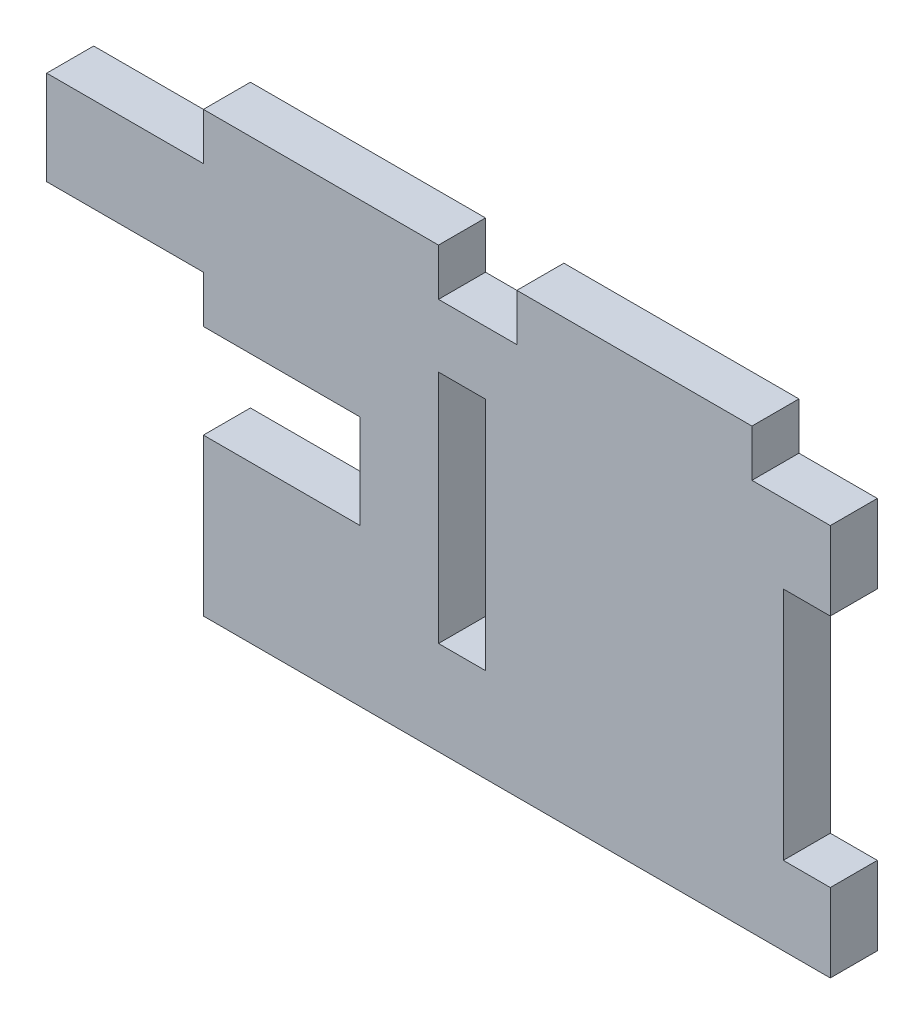
SolidWorks part; units mm, degrees
ref_plane "Front Plane" through (0, 0, 0) normal (0, 0, 1) x (1, 0, 0)
ref_plane "Top Plane" through (0, 0, 0) normal (0, 1, 0) x (1, 0, 0)
ref_plane "Right Plane" through (0, 0, 0) normal (1, 0, 0) x (0, 0, -1)
sketch "Sketch2" plane through (0, 0, 0) normal (0, 0, 1) x (1, 0, 0)
  line L0 (-22.0738, 7.8629) -> (-22.0738, 10.8629)
  line L1 (17.9262, 7.8629) -> (12.9262, 7.8629)
  line L2 (17.9262, 7.8629) -> (17.9262, -17.1371)
  line L3 (17.9262, -17.1371) -> (-32.0738, -17.1371)
  line L4 (-32.0738, 7.8629) -> (-32.0738, -17.1371)
  line L5 (17.9262, 2.8629) -> (14.9262, 2.8629)
  line L6 (-22.0738, 10.8629) -> (-7.0738, 10.8629)
  line L7 (17.9262, -12.1371) -> (14.9262, -12.1371)
  line L8 (14.9262, 2.8629) -> (14.9262, -12.1371)
  line L9 (-4.0738, -11.1532) -> (-7.0738, -11.1532)
  line L10 (-4.0738, -11.1532) -> (-4.0738, 3.8468)
  line L11 (-4.0738, 3.8468) -> (-7.0738, 3.8468)
  line L12 (-7.0738, -11.1532) -> (-7.0738, 3.8468)
  line L13 (-27.0738, -1.1371) -> (-12.0738, -1.1371)
  line L14 (-27.0738, -1.1371) -> (-27.0738, -7.1371)
  line L15 (-27.0738, -7.1371) -> (-12.0738, -7.1371)
  line L16 (-12.0738, -1.1371) -> (-12.0738, -7.1371)
  line L17 (-7.0738, 10.8629) -> (-7.0738, 7.8629)
  line L18 (-2.0738, 7.8629) -> (-2.0738, 10.8629)
  line L19 (-2.0738, 10.8629) -> (12.9262, 10.8629)
  line L20 (12.9262, 10.8629) -> (12.9262, 7.8629)
  line L21 (-22.0738, 7.8629) -> (-32.0738, 7.8629)
  line L22 (-2.0738, 7.8629) -> (-7.0738, 7.8629)
  point P8 (-4.0738, -3.8952)
  dimension "D1" = 3
  dimension "D2" = 15
  dimension "D3" = 22
  dimension "D4" = 3
  dimension "D5" = 15
  dimension "D6" = 6
  dimension "D7" = 15
  dimension "D8" = 3
  dimension "D9" = 15
  dimension "D10" = 3
  dimension "D11" = 15
  dimension "D12" = 5
  dimension "D13" = 5
  dimension "D14" = 5
  dimension "D15" = 10
  dimension "D16" = 5
  dimension "D17" = 5
  dimension "D18" = 10
  dimension "D19" = 50
extrude "Boss-Extrude1" add sketch "Sketch2" along normal blind 3 contours L18 L22 L17 L6 L0 L21 L4 L3 L2 L7 L8 L5 L1 L20 L19 L13 L16 L15 L14 L9 L12 L11 L10 region at (-21.5007, 9.3629, 0)
sketch "Sketch4" plane through (0, 0, 3) normal (0, 0, 1) x (1, 0, 0)
  line L1 (17.9262, -17.1371) -> (-32.0738, -17.1371) construction
  line L2 (-32.0738, 1.8629) -> (-22.523, 1.8629)
  line L3 (-22.0738, -17.1371) -> (-22.0738, 1.8629)
  line L4 (-22.0738, 1.8629) -> (-22.523, 1.8629)
  line L5 (-22.0738, -17.1371) -> (-32.0738, -17.1371)
  line L6 (-32.0738, -17.1371) -> (-32.0738, 1.8629)
  line L7 (-32.0738, 7.8629) -> (-32.0738, -17.1371) construction
extrude "Cut-Extrude1" cut sketch "Sketch4" against normal through all
